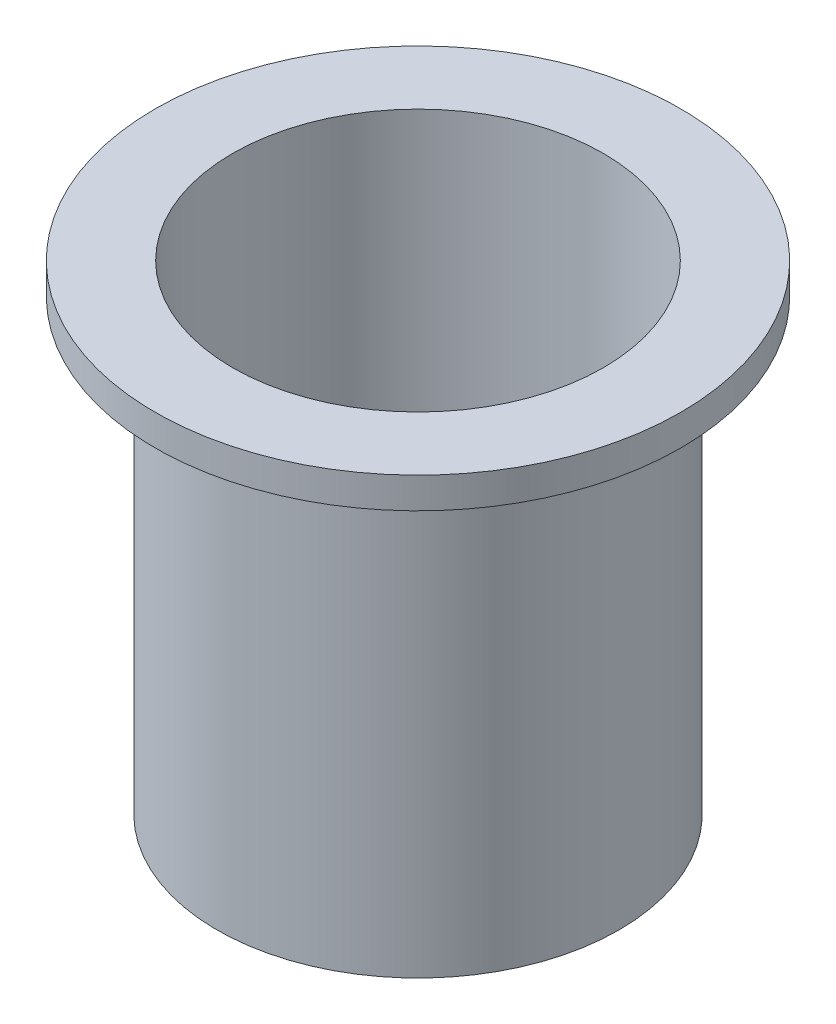
SolidWorks part; units mm, degrees
material "Delrin 2700 NC010, Low Viscosity Acetal Copolymer (SS)"
ref_plane "Front Plane" through (0, 0, 0) normal (0, 0, 1) x (1, 0, 0)
ref_plane "Top Plane" through (0, 0, 0) normal (0, 1, 0) x (1, 0, 0)
ref_plane "Right Plane" through (0, 0, 0) normal (1, 0, 0) x (0, 0, -1)
sketch "Sketch1" plane through (0, 0, 0) normal (0, 0, 1) x (1, 0, 0)
  line L0 (0, -554.3926) -> (0, 27165.2366) construction
  line L1 (41.275, 0) -> (30.744, 0)
  line L2 (41.275, 0) -> (41.275, 92.075)
  line L3 (38.1, 98.425) -> (41.275, 98.425)
  line L9 (38.1, 98.425) -> (38.1, 3.175)
  line L10 (41.275, 98.425) -> (53.975, 98.425)
  line L11 (30.744, 0) -> (0, 0)
  line L12 (41.275, 92.075) -> (53.975, 92.075)
  line L13 (53.975, 98.425) -> (53.975, 92.075)
  line L14 (0, 0) -> (0, 3.175)
  line L15 (0, 3.175) -> (38.1, 3.175)
  dimension "D1" = 76.2
  dimension "D2" = 3.175
  dimension "D4" = 3.175
  dimension "D5" = 88.9
  dimension "D8" = 6.35
  dimension "D9" = 12.7
revolve "Revolve1" add sketch "Sketch1" angle 360 about L0
sketch "Sketch2" plane through (0, 3.175, 0) normal (0, 1, 0) x (1, 0, 0)
  circle A0 centre (0, 19.05) radius 3.175
  dimension "D1" = 6.35
  dimension "D2" = 19.05
extrude "Cut-Extrude1" cut sketch "Sketch2" against normal through all
pattern_circular "CirPattern1" count 6 over 360 about axis through (0, -554.3926, 0) along (0, -1, 0) of "Cut-Extrude1"
